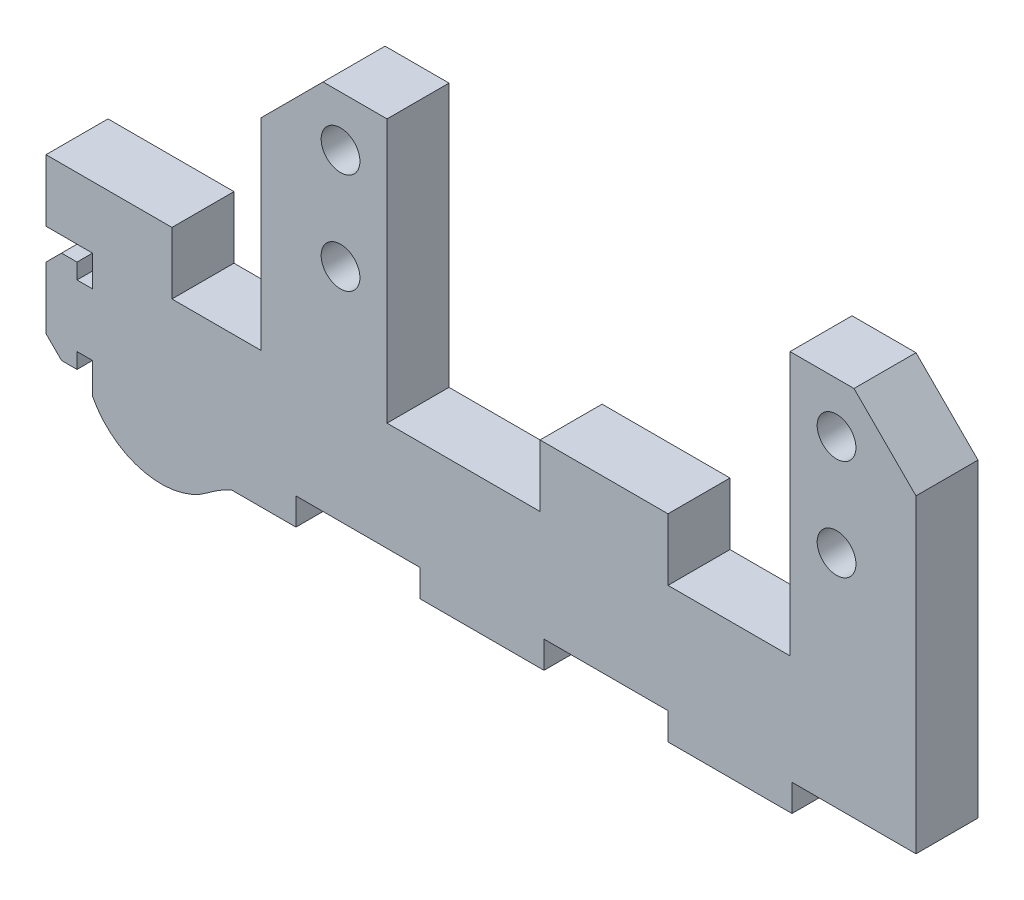
SolidWorks part; units mm, degrees
ref_plane "Front Plane" through (0, 0, 0) normal (0, 0, 1) x (1, 0, 0)
ref_plane "Top Plane" through (0, 0, 0) normal (0, 1, 0) x (1, 0, 0)
ref_plane "Right Plane" through (0, 0, 0) normal (1, 0, 0) x (0, 0, -1)
sketch "Sketch1" plane through (0, 136.6763, 0) normal (0, 1, 0) x (1, 0, 0)
  line L0 (-27.651, -32.4827) -> (-27.651, -60.4545) construction
  line L1 (-103.851, -54.1033) -> (-90.951, -54.1033)
  line L2 (-103.851, -54.1033) -> (-103.851, -60.4533)
  line L3 (-103.851, -60.4533) -> (-90.951, -60.4533)
  line L4 (-90.951, -54.1033) -> (-90.951, -60.4533)
  line L5 (-68.926, -54.1033) -> (-81.826, -54.1033)
  line L6 (-68.926, -54.1033) -> (-68.926, -60.4533)
  line L7 (-68.926, -60.4533) -> (-81.826, -60.4533)
  line L8 (-81.826, -54.1033) -> (-81.826, -60.4533)
  line L9 (-53.251, -54.1033) -> (-40.151, -54.1033)
  line L10 (-53.251, -54.1033) -> (-53.251, -60.4533)
  line L11 (-53.251, -60.4533) -> (-40.151, -60.4533)
  line L12 (-40.151, -54.1033) -> (-40.151, -60.4533)
  line L13 (-27.651, -54.1033) -> (-14.751, -54.1033)
  line L14 (-27.651, -54.1033) -> (-27.651, -60.4533)
  line L15 (-27.651, -60.4533) -> (-14.751, -60.4533)
  line L16 (-14.751, -54.1033) -> (-14.751, -60.4533)
  dimension "D1" = 12.9
  dimension "D2" = 13.1
  dimension "D3" = 12.9
  dimension "D4" = 12.9
  dimension "D5" = 50.6
extrude "Boss-Extrude1" add sketch "Sketch1" against normal blind 6.35
sketch "Sketch2" plane through (0, 130.3263, 0) normal (0, -1, 0) x (-1, 0, 0)
  line L1 (103.851, -60.4533) -> (14.951, -60.4533)
  line L2 (103.851, -60.4533) -> (103.851, -54.1033)
  line L3 (103.851, -54.1033) -> (14.951, -54.1033)
  line L4 (14.951, -60.4533) -> (14.951, -54.1033)
  dimension "D1" = 6.35
  dimension "D2" = 88.9
extrude "Boss-Extrude2" add sketch "Sketch2" along normal blind 12.7
sketch "Sketch3" plane through (0, 136.6763, 0) normal (0, 1, 0) x (1, 0, 0)
  line L1 (-68.926, -54.1033) -> (-81.826, -54.1033)
  line L2 (-68.926, -54.1033) -> (-68.926, -60.4533)
  line L3 (-68.926, -60.4533) -> (-81.826, -60.4533)
  line L4 (-81.826, -54.1033) -> (-81.826, -60.4533)
  line L5 (-14.751, -54.1033) -> (-27.651, -54.1033)
  line L6 (-14.751, -54.1033) -> (-14.751, -60.4533)
  line L7 (-14.751, -60.4533) -> (-27.651, -60.4533)
  line L8 (-27.651, -54.1033) -> (-27.651, -60.4533)
extrude "Boss-Extrude3" add sketch "Sketch3" along normal up to surface (20.6375 mm away)
chamfer "Chamfer1" distance 6.35 angle 45 2 edges at (-14.751, 157.3138, 57.2783) (-81.826, 157.3138, 57.2783)
sketch "Sketch4" plane through (0, 0, 60.4533) normal (0, 0, 1) x (1, 0, 0)
  circle A0 centre (-73.6885, 152.1544) radius 1.9844
  circle A1 centre (-73.6885, 141.8357) radius 1.9844
  circle A2 centre (-22.8885, 141.8357) radius 1.9844
  circle A3 centre (-22.8885, 152.1544) radius 1.9844
extrude "Cut-Extrude1" cut sketch "Sketch4" against normal through all
sketch "Sketch8" plane through (0, 0, 60.4533) normal (0, 0, 1) x (1, 0, 0)
  line L0 (-103.851, 123.9763) -> (-14.951, 123.9763) construction
  line L1 (-103.851, 117.6263) -> (-103.851, 136.6763) construction
  line L2 (-99.0885, 117.6263) -> (-99.0885, 120.8013)
  line L3 (-103.851, 130.3263) -> (-102.9247, 130.3263)
  line L4 (-103.851, 130.3263) -> (-103.851, 128.7388)
  line L5 (-103.851, 128.7388) -> (-100.676, 128.7388)
  line L6 (-103.851, 117.6263) -> (-102.9247, 117.6263)
  line L7 (-103.851, 130.3263) -> (-100.676, 128.7388) construction
  line L8 (-103.851, 128.7388) -> (-102.9247, 130.3263) construction
  line L9 (-102.9247, 130.3263) -> (-99.0885, 130.3263)
  line L10 (-100.676, 128.7388) -> (-100.676, 127.1513)
  line L11 (-100.676, 127.1513) -> (-99.0885, 127.1513)
  line L12 (-99.0885, 130.3263) -> (-99.0885, 127.1513)
  line L13 (-102.9247, 130.3263) -> (-99.0885, 127.1513) construction
  line L14 (-100.676, 127.1513) -> (-99.0885, 130.3263) construction
  line L15 (-102.9247, 117.6263) -> (-99.0885, 117.6263)
  line L16 (-103.851, 117.6263) -> (-103.851, 119.2138)
  line L17 (-103.851, 119.2138) -> (-100.676, 119.2138)
  line L18 (-100.676, 119.2138) -> (-100.676, 120.8013)
  line L19 (-100.676, 120.8013) -> (-99.0885, 120.8013)
  point P9 (-103.1339, 129.9678)
  point P13 (-100.2113, 128.0806)
  dimension "D1" = 6.35
  dimension "D2" = 4.7625
  dimension "D3" = 3.175
  dimension "D4" = 1.5875
  dimension "D5" = 3.175
  dimension "D6" = 3.175
extrude "Cut-Extrude3" cut sketch "Sketch8" against normal through all
chamfer "Chamfer2" distance 1.5875 angle 45 2 edges at (-103.851, 128.7388, 57.2783) (-103.851, 119.2138, 57.2783)
sketch "Sketch12" plane through (-14.951, 0, 0) normal (1, 0, 0) x (0, 0, -1)
  line L1 (-60.4533, 117.6263) -> (-54.1033, 117.6263)
  line L2 (-60.4533, 117.6263) -> (-60.4533, 130.3263)
  line L3 (-60.4533, 130.3263) -> (-54.1033, 130.3263)
  line L4 (-54.1033, 117.6263) -> (-54.1033, 130.3263)
extrude "Boss-Extrude6" add sketch "Sketch12" along normal up to surface (0.2 mm away) up to face at (-14.751, 140.645, 57.2783)
sketch "Sketch13" plane through (0, 0, 60.4533) normal (0, 0, 1) x (1, 0, 0)
  line L0 (-14.751, 117.6263) -> (-99.0885, 117.6263) construction
  line L1 (-85.0232, 117.6263) -> (-99.0885, 117.6263)
  arc A0 (-99.0885, 117.6263) -> (-85.0232, 117.6263) centre (-92.0558, 121.3068) ccw
  dimension "D1" = 7.9375
extrude "Boss-Extrude7" add sketch "Sketch13" against normal blind 6.35
fillet "Fillet12" radius 12.7 1 edges at (-85.0232, 117.6263, 57.2783)
sketch "Sketch14" plane through (0, 0, 60.4533) normal (0, 0, 1) x (1, 0, 0)
  line L0 (-40.151, 117.6263) -> (-52.851, 117.6263)
  line L1 (-14.751, 117.6263) -> (-27.451, 117.6263)
  line L2 (-14.751, 117.6263) -> (-14.751, 119.2138)
  line L3 (-14.751, 119.2138) -> (-27.451, 119.2138)
  line L4 (-27.451, 117.6263) -> (-27.451, 119.2138)
  line L5 (-52.851, 117.6263) -> (-52.851, 119.2138)
  line L6 (-40.151, 119.2138) -> (-52.851, 119.2138)
  line L7 (-40.151, 117.6263) -> (-40.151, 119.2138)
  line L8 (-65.551, 117.6263) -> (-78.251, 117.6263)
  line L9 (-78.251, 117.6263) -> (-78.251, 119.2138)
  line L10 (-65.551, 119.2138) -> (-78.251, 119.2138)
  line L11 (-65.551, 117.6263) -> (-65.551, 119.2138)
  line L16 (-103.651, 117.6263) -> (-103.651, 119.2138) [skipped]
  line L17 (-90.951, 119.2138) -> (-103.651, 119.2138) [skipped]
  line L18 (-90.951, 117.6263) -> (-103.651, 117.6263) [skipped]
  line L19 (-90.951, 117.6263) -> (-90.951, 119.2138) [skipped]
  dimension "D1" = 12.7
  dimension "D2" = 1.5875
  dimension "D3" = 4
extrude "Cut-Extrude5" cut sketch "Sketch14" against normal through all
sketch "Sketch15" plane through (0, 0, 60.4533) normal (0, 0, 1) x (1, 0, 0)
  line L0 (-65.551, 117.6263) -> (-65.551, 116.4388)
  line L1 (-27.451, 117.6263) -> (-40.151, 117.6263)
  line L2 (-27.451, 117.6263) -> (-27.451, 116.4388)
  line L3 (-27.451, 116.4388) -> (-40.151, 116.4388)
  line L4 (-40.151, 117.6263) -> (-40.151, 116.4388)
  line L5 (-52.851, 117.6263) -> (-52.851, 116.4388)
  line L6 (-52.851, 116.4388) -> (-65.551, 116.4388)
  line L7 (-90.951, 117.6263) -> (-90.951, 116.4388)
  line L8 (-78.251, 117.6263) -> (-78.251, 116.4388)
  line L9 (-78.251, 116.4388) -> (-90.951, 116.4388)
  line L10 (-52.851, 117.6263) -> (-65.551, 117.6263)
  line L11 (-78.251, 117.6263) -> (-90.951, 117.6263)
  dimension "D1" = 1.1875
  dimension "D2" = 3
extrude "Boss-Extrude8" add sketch "Sketch15" against normal blind 6.35
